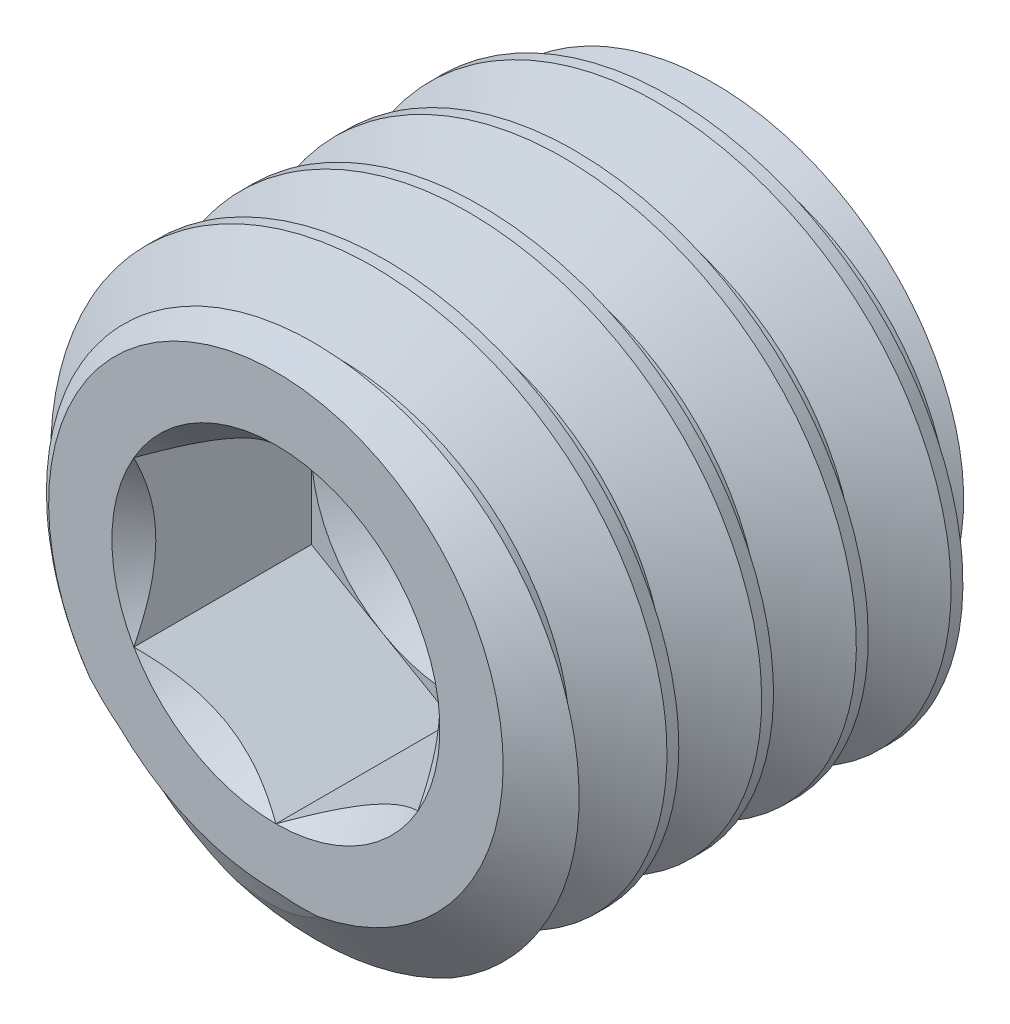
SolidWorks part; units mm, degrees
ref_plane "Front" through (0, 0, 0) normal (0, 0, 1) x (1, 0, 0)
ref_plane "Top" through (0, 0, 0) normal (0, 1, 0) x (1, 0, 0)
ref_plane "Right" through (0, 0, 0) normal (1, 0, 0) x (0, 0, -1)
ref_axis "Center Line Axis" through (0, 0, -88.8886) along (0, 0, 1)
sketch "Body Sketch" plane through (0, 0, 0) normal (1, 0, 0) x (0, 0, -1)
  line L0 (-1.5, 0) -> (-1.5, 1.2)
  line L1 (-1.5, 1.2) -> (-1.2899, 1.5)
  line L2 (-1.2899, 1.5) -> (0.7466, 1.5)
  line L3 (0.7466, 1.5) -> (1.5, 0.195)
  line L4 (-1.5, 1.2) -> (-1.5, -1.2) construction
  line L5 (1.5, 0) -> (-1.5, 0)
  line L6 (0, 1.5) -> (0, -1.5) construction
  line L8 (1.5, 0.195) -> (1.5, 0)
  line L9 (-1.5, -1.5) -> (1.5, -1.5) construction
  line L10 (1.5, 0.195) -> (1.5, -0.195) construction
  line L11 (1.5, -0.195) -> (0.7466, -1.5) construction
  line L13 (1.5, 0.195) -> (1.3874, 0) construction
  line L15 (1.3874, 0) -> (1.5, -0.195) construction
  dimension "D3" = 35
  dimension "D7" = 2.4
  dimension "Diameter" = 3
  dimension "Length" = 3
  dimension "D2" = 0.39
  dimension "Cone Angle" = 120
  dimension "D90" = 120
revolve "Body Revolve" add sketch "Body Sketch" angle 360 about L5
ref_plane "Tip Plane" through (0, 0, -1.5) normal (0, 0, 1) x (1, 0, 0)
sketch "Spiral Sketch" plane through (0, 0, -1.5) normal (0, 0, 1) x (1, 0, 0)
  circle A0 centre (0, 0) radius 1.5 construction
  circle A1 centre (0, 0) radius 1.5
sketch "Hex Sketch" plane through (0, 0, 1.5) normal (0, 0, 1) x (1, 0, 0)
  line L1 (0, 0.866) -> (-0.75, 0.433)
  line L2 (-0.75, 0.433) -> (-0.75, -0.433)
  line L3 (-0.75, -0.433) -> (0, -0.866)
  line L4 (0, -0.866) -> (0.75, -0.433)
  line L5 (0.75, -0.433) -> (0.75, 0.433)
  line L6 (0.75, 0.433) -> (0, 0.866)
  circle A0 centre (0, 0) radius 0.75 construction
  dimension "Hex" = 1.5
extrude "Hex Extrude" cut sketch "Hex Sketch" against normal blind 0.9375
sketch "Hex Entry Sketch" plane through (0, 0, 1.5) normal (0, 0, 1) x (1, 0, 0)
  circle A0 centre (0, 0) radius 0.866
extrude "Hex Entry Extrude" cut sketch "Hex Entry Sketch" against normal through all draft 45
sketch "Hex Bottom Sketch" plane through (0, 0, 0.5625) normal (0, 0, 1) x (1, 0, 0)
  circle A0 centre (0, 0) radius 0.75 construction
  circle A1 centre (0, 0) radius 0.75
extrude "Hex Bottom Extrude" cut sketch "Hex Bottom Sketch" against normal through all draft 60
curve "Helix/Spiral" pitch 0.5 height 3.5 radius 1.5 centre (0, 0, -1.5) axis (0, 0, 1) start towards (0, 1, 0)
sketch "Sketch28" plane through (0, 0, 0) normal (1, 0, 0) x (0, 0, -1)
  line L0 (1.5, 1.5) -> (1.9375, 1.5)
  line L1 (1.9375, 1.5) -> (1.75, 1.1752)
  line L2 (1.75, 1.1752) -> (1.6875, 1.1752)
  line L3 (1.6875, 1.1752) -> (1.5, 1.5)
  line L4 (1.5937, 1.3376) -> (1.8437, 1.3376) construction
  line L6 (-1.2899, 1.5) -> (0.7466, 1.5) construction
  line L7 (1.5, 6.7518) -> (1.5, -6.7518) construction
  dimension "D1" = 0.0625
  dimension "D3" = 60
  dimension "D2" = 0.25
sweep "Thread Sweep" cut profiles "Sketch28" path "Helix/Spiral"
ref_plane "Contact Plane 1" through (0, 0, 1.5) normal (0, 0, 1) x (1, 0, 0)
ref_plane "Contact Plane 2" through (0, 0, -1.5) normal (0, 0, -1) x (-1, 0, 0)
ref_axis "Center Axis 1" through (0, 0, 49.8835) along (0, 0, -1)
equation "\"D7@Body Sketch\" = \"Diameter@Body Sketch\" * .8"
equation "\"D1@Sketch28\" = \"D4@Helix/Spiral\" * .125"
equation "\"D3@Helix/Spiral\" = \"Length@Body Sketch\" + \"D4@Helix/Spiral\""
equation "\"hex Depth@Hex Extrude\" = \"Hex@Hex Sketch\" * .625"
equation "\"D2@Sketch28\" = \"D4@Helix/Spiral\" * .5"
equation "\"D2@Body Sketch\" = \"Diameter@Body Sketch\" * .13"
equation "\"D90@Body Sketch\" = \"Cone Angle@Body Sketch\""
equation "\"Diameter\"= 3mm"
equation "\"Thread Pitch\"= 0.5mm"
equation "\"Hex Size\"= 1.5mm"
equation "\"Diameter@Body Sketch\" = \"Diameter\""
equation "\"Hex@Hex Sketch\" = \"Hex Size\""
equation "\"D4@Helix/Spiral\"=\"Thread Pitch\""
